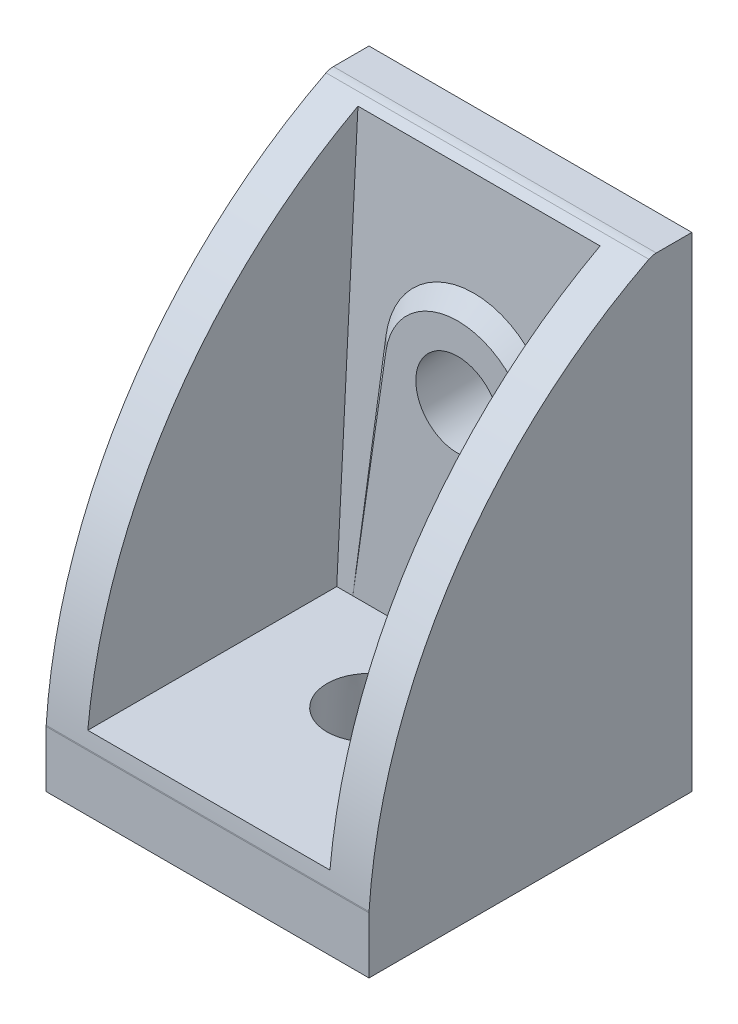
SolidWorks part; units mm, degrees
ref_plane "Front Plane" through (0, 0, 0) normal (0, 0, 1) x (1, 0, 0)
ref_plane "Top Plane" through (0, 0, 0) normal (0, 1, 0) x (1, 0, 0)
ref_plane "Right Plane" through (0, 0, 0) normal (1, 0, 0) x (0, 0, -1)
ref_plane "Plane1" through (0, 0, 0) normal (1, 0, 0) x (0, 0, -1)
sketch "Sketch1" plane through (0, 0, 0) normal (1, 0, 0) x (0, 0, -1)
  line L0 (-20, 3.4921) -> (-20, 0)
  line L1 (-20, 0) -> (0, 0)
  line L2 (0, 0) -> (0, 30)
  line L3 (0, 30) -> (-2.2048, 30)
  arc A0 (-2.2048, 30) -> (-2.6607, 29.89) centre (-2.2048, 29) ccw
  arc A1 (-2.6607, 29.89) -> (-19.9977, 3.5593) centre (11.93, 1.41) ccw
  arc A2 (-19.9977, 3.5593) -> (-20, 3.4921) centre (-19, 3.4921) ccw
extrude "Boss-Extrude1" add sketch "Sketch1" along normal blind 20
ref_plane "Plane2" through (10, 0, 0) normal (1, 0, 0) x (0, 0, -1)
sketch "Sketch2" plane through (10, 0, 0) normal (1, 0, 0) x (0, 0, -1)
  line L0 (-20, 30) -> (-20, 4.5)
  line L1 (-20, 4.5) -> (-4.5, 4.5)
  line L2 (-4.5, 4.5) -> (-3.1636, 30)
  line L3 (-3.1636, 30) -> (-20, 30)
extrude "Cut-Extrude1" cut sketch "Sketch2" against normal blind 7.5 and the other way blind 7.5
ref_plane "Plane3" through (10, 0, 0) normal (1, 0, 0) x (0, 0, -1)
sketch "Sketch3" plane through (10, 0, 0) normal (1, 0, 0) x (0, 0, -1)
  line L0 (-0.5, 26.5) -> (-0.5, 23.5)
  line L1 (-0.5, 23.5) -> (1, 24.366)
  line L2 (1, 24.366) -> (1, 25.634)
  line L3 (1, 25.634) -> (-0.5, 26.5)
extrude "Boss-Extrude2" add sketch "Sketch3" against normal blind 3 and the other way blind 3
ref_plane "Plane4" through (10, 0, 0) normal (1, 0, 0) x (0, 0, -1)
sketch "Sketch4" plane through (10, 0, 0) normal (1, 0, 0) x (0, 0, -1)
  line L0 (-0.5, 13) -> (-0.5, 4)
  line L1 (-0.5, 4) -> (1, 4.866)
  line L2 (1, 4.866) -> (1, 12.134)
  line L3 (1, 12.134) -> (-0.5, 13)
extrude "Boss-Extrude3" add sketch "Sketch4" against normal blind 3 and the other way blind 3
ref_plane "Plane5" through (0, 0, 4.5) normal (0, 0, 1) x (1, 0, 0)
sketch "Sketch5" plane through (0, 0, 4.5) normal (0, 0, 1) x (1, 0, 0)
  line L0 (3.4955, 4.5) -> (16.5045, 4.5)
  line L1 (16.5045, 4.5) -> (14.4534, 18.6457)
  line L2 (5.5466, 18.6457) -> (3.4955, 4.5)
  arc A0 (14.4534, 18.6457) -> (5.5466, 18.6457) centre (10, 18) ccw
extrude "Boss-Extrude4" add sketch "Sketch5" against normal blind 2 draft 45 draft outward yes
ref_plane "Plane6" through (0, 0.5, 0) normal (0, 1, 0) x (1, 0, 0)
sketch "Sketch6" plane through (0, 0.5, 0) normal (0, 1, 0) x (1, 0, 0)
  line L0 (7.075, -12.925) -> (12.925, -12.925)
  line L1 (12.925, -12.925) -> (12.925, -7.075)
  line L2 (12.925, -7.075) -> (7.075, -7.075)
  line L3 (7.075, -7.075) -> (7.075, -12.925)
extrude "Boss-Extrude5" add sketch "Sketch6" against normal blind 1.5 draft 6
ref_plane "Plane7" through (0, 0, 0) normal (0, 1, 0) x (1, 0, 0)
sketch "Sketch7" plane through (0, 0, 0) normal (0, 1, 0) x (1, 0, 0)
  line L0 (7.075, -10.835) -> (9.165, -10.835)
  line L1 (9.165, -10.835) -> (9.165, -12.925)
  line L2 (9.165, -12.925) -> (10.835, -12.925)
  line L3 (10.835, -12.925) -> (10.835, -10.835)
  line L4 (10.835, -10.835) -> (12.925, -10.835)
  line L5 (12.925, -10.835) -> (12.925, -9.165)
  line L6 (12.925, -9.165) -> (10.835, -9.165)
  line L7 (10.835, -9.165) -> (10.835, -7.075)
  line L8 (10.835, -7.075) -> (9.165, -7.075)
  line L9 (9.165, -7.075) -> (9.165, -9.165)
  line L10 (9.165, -9.165) -> (7.075, -9.165)
  line L11 (7.075, -9.165) -> (7.075, -10.835)
extrude "Cut-Extrude2" cut sketch "Sketch7" against normal blind 1 draft 6 draft outward yes
ref_plane "Plane8" through (10, 0, 0) normal (1, 0, 0) x (0, 0, -1)
sketch "Sketch8" plane through (10, 0, 0) normal (1, 0, 0) x (0, 0, -1)
  line L0 (-4.5, 18) -> (-4.5, 20.6)
  line L1 (-4.5, 20.6) -> (0, 20.8358)
  line L2 (0, 20.8358) -> (0, 18)
  line L3 (0, 18) -> (-4.5, 18)
  line L4 (0, 18) -> (-4.5, 18) construction
revolve "Cut-Revolve1" cut sketch "Sketch8" angle 360 about L4 reverse direction yes
ref_plane "Plane9" through (10, 0, 0) normal (1, 0, 0) x (0, 0, -1)
sketch "Sketch9" plane through (10, 0, 0) normal (1, 0, 0) x (0, 0, -1)
  line L0 (-10, 4.5) -> (-7.4, 4.5)
  line L1 (-7.4, 4.5) -> (-7.1118, -1)
  line L2 (-7.1118, -1) -> (-10, -1)
  line L3 (-10, -1) -> (-10, 4.5)
  line L4 (-10, -1) -> (-10, 4.5) construction
revolve "Cut-Revolve2" cut sketch "Sketch9" angle 360 about L4 reverse direction yes
